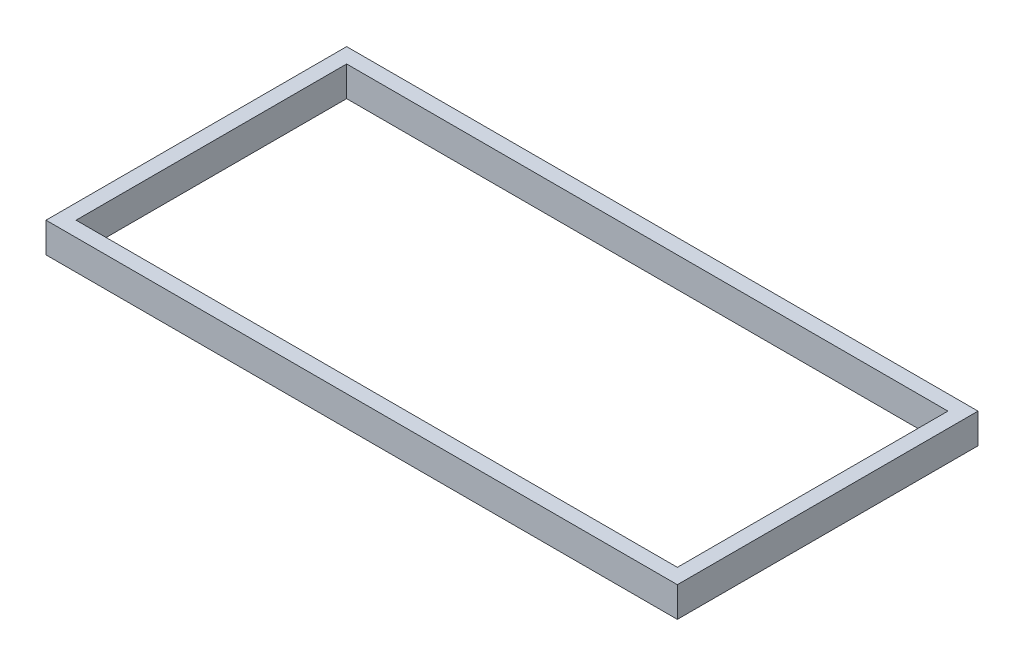
SolidWorks part; units mm, degrees
ref_plane "Front Plane" through (0, 0, 0) normal (0, 0, 1) x (1, 0, 0)
ref_plane "Top Plane" through (0, 0, 0) normal (0, 1, 0) x (1, 0, 0)
ref_plane "Right Plane" through (0, 0, 0) normal (1, 0, 0) x (0, 0, -1)
sketch "Sketch1" plane through (0, 0, 0) normal (0, 1, 0) x (1, 0, 0)
  line L1 (-1050, -500) -> (1050, -500)
  line L2 (-1050, -500) -> (-1050, 500)
  line L3 (-1050, 500) -> (1050, 500)
  line L4 (1050, -500) -> (1050, 500)
  line L5 (-1050, -500) -> (1050, 500) construction
  line L6 (-1050, 500) -> (1050, -500) construction
  point P0 (0, 0)
  dimension "D1" = 2100
  dimension "D2" = 1000
extrude "Boss-Extrude1" add sketch "Sketch1" along normal mid plane 100
sketch "Sketch2" plane through (0, 50, 0) normal (0, 1, 0) x (1, 0, 0)
  line L1 (-1000, -450) -> (1000, -450)
  line L2 (-1000, -450) -> (-1000, 450)
  line L3 (-1000, 450) -> (1000, 450)
  line L4 (1000, -450) -> (1000, 450)
  line L5 (-1000, -450) -> (1000, 450) construction
  line L6 (-1000, 450) -> (1000, -450) construction
  point P0 (0, 0)
  dimension "D1" = 2000
  dimension "D2" = 900
extrude "Cut-Extrude1" cut sketch "Sketch2" against normal up to next
